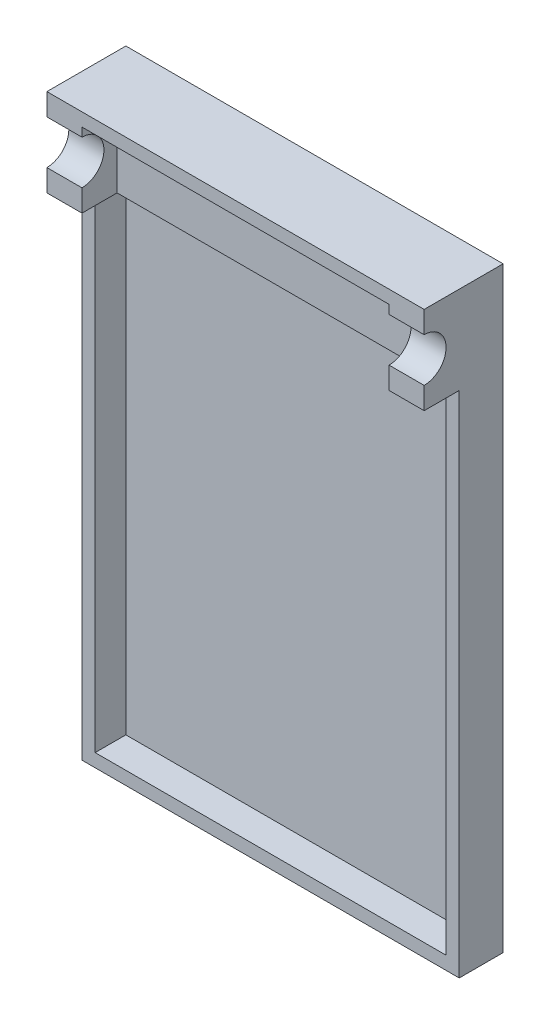
SolidWorks part; units mm, degrees
note: The reader was unsure of these and kept them because the rebuilt part matched: shared geometry of "Çizim1<2>".
ref_plane "Ön Düzlem" through (0, 0, 0) normal (0, 0, 1) x (1, 0, 0)
ref_plane "Üst Düzlem" through (0, 0, 0) normal (0, 1, 0) x (1, 0, 0)
ref_plane "Sağ Düzlem" through (0, 0, 0) normal (1, 0, 0) x (0, 0, -1)
sketch "Çizim1" plane through (0, 0, 0) normal (0, 0, 1) x (1, 0, 0)
  line L0 (-20.6488, 89.6274) -> (-20.6488, -40.3726)
  line L1 (-20.6488, 89.6274) -> (59.3512, 89.6274)
  line L2 (59.3512, 89.6274) -> (59.3512, -40.3726)
  line L3 (59.3512, -40.3726) -> (-20.6488, -40.3726)
  line L4 (62.3512, -43.3726) -> (-23.6488, -43.3726)
  line L5 (-23.6488, 92.6274) -> (-23.6488, -43.3726)
  line L6 (-23.6488, 92.6274) -> (62.3512, 92.6274)
  line L7 (62.3512, 92.6274) -> (62.3512, -43.3726)
extrude "Yükseklik-Ekstrüzyon1" add sketch "Çizim1" along normal blind 10
extrude "Yükseklik-Ekstrüzyon2" add sketch "Çizim1<2>" along normal blind 3 contours L3 L2 L1 L0
sketch "Çizim1<2>" plane through (0, 0, 0) normal (0, 0, 1) x (1, 0, 0) same geometry as "Çizim1"
sketch "Çizim2" plane through (-23.6488, 0, 0) normal (-1, 0, 0) x (0, 0, 1)
  line L0 (10, 92.6274) -> (10, 87.6274)
  line L1 (10, 92.6274) -> (10, -43.3726) construction
  line L3 (18, 87.6274) -> (18, 77.6274)
  line L5 (10, 77.6274) -> (10, 87.6274)
  line L7 (10, 77.6274) -> (10, 72.6274)
  line L9 (18, 77.6274) -> (18, 75.6274)
  line L10 (18, 89.6274) -> (18, 87.6274)
  line L11 (18, 89.6274) -> (18, 92.6274)
  line L12 (18, 92.6274) -> (10, 92.6274)
  line L13 (18, 75.6274) -> (18, 72.6274)
  line L14 (18, 72.6274) -> (10, 72.6274)
  arc A0 (18, 87.6274) -> (18, 77.6274) centre (18, 82.6274) ccw
extrude "Yükseklik-Ekstrüzyon3" add sketch "Çizim2" against normal through all
sketch "Çizim3" plane through (0, 92.6274, 0) normal (0, 1, 0) x (1, 0, 0)
  line L0 (-15.6488, -10) -> (54.3512, -10)
  line L3 (54.3512, -18) -> (-15.6488, -18)
  line L8 (-15.6488, -10) -> (54.3512, -10)
  line L9 (-15.6488, -10) -> (-15.6488, -18)
  line L10 (-15.6488, -18) -> (54.3512, -18)
  line L11 (54.3512, -10) -> (54.3512, -18)
sketch "Çizim5" plane through (0, 72.6274, 0) normal (0, -1, 0) x (1, 0, 0)
  line L0 (-15.6488, 10) -> (-15.6488, 3)
  line L1 (-15.6488, 18) -> (54.3512, 18)
  line L2 (-15.6488, 18) -> (-15.6488, 10)
  line L4 (54.3512, 18) -> (54.3512, 10)
  line L5 (-15.6488, 3) -> (54.3512, 3)
  line L6 (54.3512, 3) -> (54.3512, 10)
extrude "Kes-Ekstrüzyon2" cut sketch "Çizim5" against normal blind 17 from offset 0
sketch "Çizim6" plane through (-20.6488, 0, 0) normal (1, 0, 0) x (0, 0, -1)
  line L1 (0, -43.3726) -> (0, 92.6274) construction
  line L3 (-10, 72.6274) -> (0, 82.6274)
  line L4 (-10, 72.6274) -> (-10, 92.6274)
  line L5 (-10, 92.6274) -> (0, 92.6274)
  line L6 (0, 92.6274) -> (0, 82.6274)
extrude "Yükseklik-Ekstrüzyon4" add sketch "Çizim6" along normal up to surface (80 mm away) up to face at (59.3512, 34.2274, 7.2)
